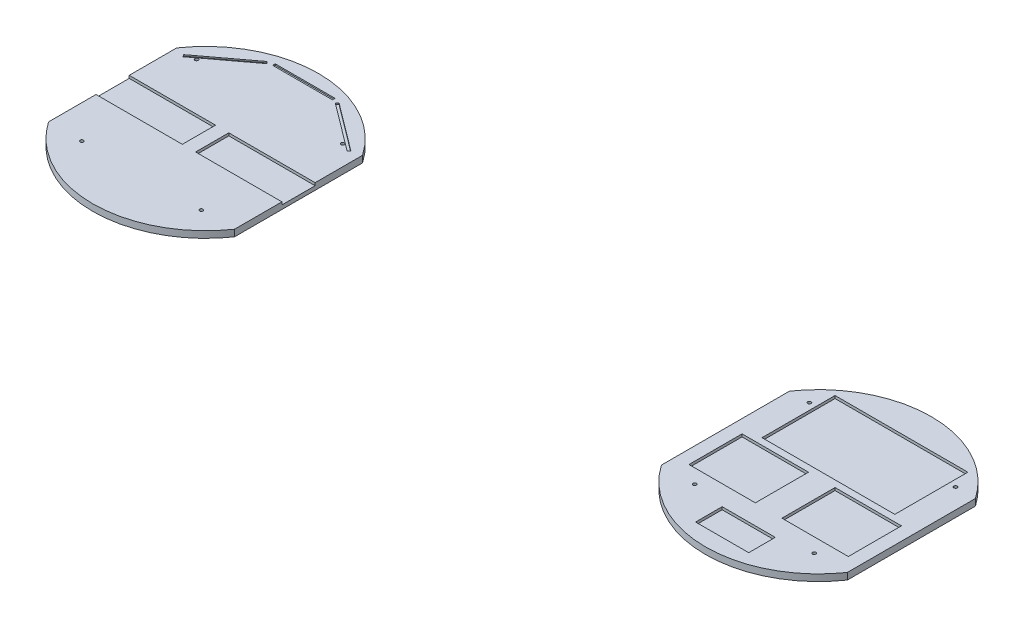
SolidWorks part; units mm, degrees
ref_plane "Front Plane" through (0, 0, 0) normal (0, 0, 1) x (1, 0, 0)
ref_plane "Top Plane" through (0, 0, 0) normal (0, 1, 0) x (1, 0, 0)
ref_plane "Right Plane" through (0, 0, 0) normal (1, 0, 0) x (0, 0, -1)
sketch "Sketch2" plane through (0, 0, 0) normal (0, 1, 0) x (1, 0, 0)
  line L0 (70, -48.2183) -> (70, 48.2183)
  line L1 (85, 0) -> (70, 0)
  line L2 (363.9575, 64.1342) -> (365.1582, 62.5347)
  line L3 (-85, 0) -> (-70, 0)
  line L4 (-70, -48.2183) -> (-70, 48.2183)
  line L5 (-22.5, 75) -> (22.5, 75)
  line L6 (0, 85) -> (0, 75)
  line L7 (70, 12.5) -> (5, 12.5)
  line L8 (-70, -12.5) -> (-5, -12.5)
  line L9 (-70, -12.5) -> (-70, 12.5)
  line L10 (-70, 12.5) -> (-5, 12.5)
  line L11 (-5, -12.5) -> (-5, 12.5)
  line L12 (-63.0208, 46.4718) -> (-27.0329, 73.4879)
  line L13 (478.9844, -44.0639) -> (478.9844, 52.3726)
  line L14 (5, -12.5) -> (5, 12.5)
  line L15 (70, -12.5) -> (5, -12.5)
  line L16 (70, -12.5) -> (70, 12.5)
  line L17 (-45.0269, 59.9798) -> (-51.0305, 67.9771)
  line L18 (45.0269, 59.9798) -> (51.0305, 67.9771)
  line L19 (63.0208, 46.4718) -> (27.0329, 73.4879)
  line L20 (933.5091, -37.1187) -> (933.5091, 59.3178)
  line L21 (347.1643, 49.0267) -> (383.1522, 76.0428)
  line L22 (408.9844, 79.1544) -> (408.9844, 77.1544)
  line L23 (338.9844, -44.0639) -> (338.9844, 52.3726)
  line L24 (386.4844, 79.1544) -> (431.4844, 79.1544)
  line L25 (408.9844, 89.1544) -> (408.9844, 79.1544)
  line L26 (478.9844, 16.6544) -> (413.9844, 16.6544)
  line L27 (338.9844, -8.3456) -> (403.9844, -8.3456)
  line L28 (338.9844, -8.3456) -> (338.9844, 16.6544)
  line L29 (338.9844, 16.6544) -> (403.9844, 16.6544)
  line L30 (403.9844, -8.3456) -> (403.9844, 16.6544)
  line L31 (345.9635, 50.6261) -> (381.9514, 77.6423)
  line L32 (413.9844, -8.3456) -> (413.9844, 16.6544)
  line L33 (478.9844, -8.3456) -> (413.9844, -8.3456)
  line L34 (478.9844, -8.3456) -> (478.9844, 16.6544)
  line L35 (363.9575, 64.1342) -> (357.9539, 72.1315)
  line L36 (454.0113, 64.1342) -> (460.0148, 72.1315)
  line L37 (471.6266, 50.9104) -> (436.0173, 77.6423)
  line L38 (793.5091, -37.1187) -> (793.5091, 59.3178)
  line L39 (386.4844, 77.1544) -> (431.4844, 77.1544)
  line L43 (813.5091, 18.5996) -> (913.5091, 18.5996)
  line L44 (813.5091, 18.5996) -> (813.5091, 73.5996)
  line L45 (813.5091, 73.5996) -> (913.5091, 73.5996)
  line L46 (913.5091, 18.5996) -> (913.5091, 73.5996)
  line L47 (813.5091, 18.5996) -> (913.5091, 73.5996) construction
  line L48 (813.5091, 73.5996) -> (913.5091, 18.5996) construction
  line L52 (454.0113, 64.1342) -> (452.8105, 62.5347)
  line L54 (873.5091, 13.5996) -> (923.5091, 13.5996)
  line L55 (923.5091, -26.4004) -> (923.5091, 13.5996)
  line L60 (873.5091, -26.4004) -> (923.5091, -26.4004)
  line L61 (853.5091, -26.4004) -> (803.5091, -26.4004)
  line L62 (853.5091, -26.4004) -> (853.5091, 13.5996)
  line L63 (853.5091, 13.5996) -> (803.5091, 13.5996)
  line L64 (803.5091, -26.4004) -> (803.5091, 13.5996)
  line L65 (853.5091, -26.4004) -> (803.5091, 13.5996) construction
  line L66 (853.5091, 13.5996) -> (803.5091, -26.4004) construction
  line L67 (873.5091, -26.4004) -> (873.5091, 13.5996)
  line L71 (470.4259, 49.3109) -> (434.8166, 76.0428)
  line L72 (436.0173, 77.6423) -> (434.8166, 76.0428)
  line L73 (843.5091, -61.4004) -> (883.5091, -61.4004)
  line L74 (843.5091, -61.4004) -> (843.5091, -41.4004)
  line L75 (843.5091, -41.4004) -> (883.5091, -41.4004)
  line L76 (883.5091, -61.4004) -> (883.5091, -41.4004)
  line L77 (843.5091, -61.4004) -> (883.5091, -41.4004) construction
  line L78 (843.5091, -41.4004) -> (883.5091, -61.4004) construction
  line L79 (470.4259, 49.3109) -> (471.6266, 50.9104)
  line L80 (381.9514, 77.6423) -> (383.1522, 76.0428)
  line L81 (347.1643, 49.0267) -> (345.9635, 50.6261)
  line L82 (386.4844, 79.1544) -> (386.4844, 77.1544)
  line L83 (431.4844, 79.1544) -> (431.4844, 77.1544)
  circle A0 centre (0, 0) radius 85
  arc A1 (338.9844, -44.0639) -> (478.9844, -44.0639) centre (408.9844, 4.1544) ccw
  arc A2 (478.9844, 52.3726) -> (338.9844, 52.3726) centre (408.9844, 4.1544) ccw
  arc A3 (793.5091, -37.1187) -> (933.5091, -37.1187) centre (863.5091, 11.0996) ccw
  arc A4 (933.5091, 59.3178) -> (793.5091, 59.3178) centre (863.5091, 11.0996) ccw
  circle A9 centre (363.9844, -44.0639) radius 1.25
  circle A10 centre (453.9844, -44.0639) radius 1.25
  circle A11 centre (818.5091, -37.1187) radius 1.25
  circle A12 centre (908.5091, -37.1187) radius 1.25
  circle A13 centre (808.5091, 59.3178) radius 1.25
  circle A14 centre (918.5091, 59.3178) radius 1.25
  circle A15 centre (353.9844, 52.3726) radius 1.25
  circle A16 centre (463.9844, 52.3726) radius 1.25
  dimension "D1" = 15
  dimension "D2" = 170
  dimension "D8" = 170
  dimension "D7" = 170
  dimension "D19" = 15
  dimension "D3" = 10
  dimension "D4" = 45
  dimension "D5" = 65
  dimension "D6" = 25
  dimension "D9" = 10
  dimension "D10" = 45
  dimension "D11" = 65
  dimension "D12" = 25
  dimension "D13" = 100
  dimension "D14" = 55
  dimension "D15" = 40
  dimension "D16" = 50
  dimension "D17" = 20
  dimension "D18" = 40
extrude "Boss-Extrude4" add sketch "Sketch2" along normal blind 4 contours L31 L80 L21 L81 | L24 L83 L39 L82 | L71 L72 L37 L79
extrude "Boss-Extrude5" add sketch "Sketch2<8>" along normal blind 3 separate body contours L27 L30 L29 L23 | L33 L13 L26 L32 region at (371.4844, 0, -4.1544) region at (446.4844, 0, -4.1544)
sketch "Sketch2<8>" plane through (0, 0, 0) normal (0, 1, 0) x (1, 0, 0) same geometry as "Sketch2"
extrude "Boss-Extrude6" add sketch "Sketch2<9>" along normal blind 5 contours L13 A2 L37 L79 L71 L72 L24 L83 L39 L82 L31 L80 L21 L81 L23 L29 L30 L27 A1 L33 L32 L26 A10 A9 A15 A16 region at (408.9878, 0, -3.15)
sketch "Sketch2<9>" plane through (0, 0, 0) normal (0, 1, 0) x (1, 0, 0) same geometry as "Sketch2"
extrude "Boss-Extrude10" add sketch "Sketch2<14>" along normal blind 3 separate body contours L43 L46 L45 L44 | L67 L60 L55 L54 | L73 L76 L75 L74 | L64 L61 L62 L63 region at (863.5091, 0, -46.0996) region at (898.5091, 0, 6.4004) region at (828.5091, 0, 6.4004) region at (863.5091, 0, 51.4004)
sketch "Sketch2<14>" plane through (0, 0, 0) normal (0, 1, 0) x (1, 0, 0) same geometry as "Sketch2"
extrude "Boss-Extrude11" add sketch "Sketch2<15>" along normal blind 5 contours L20 A4 L38 A3 A12 A11 L60 L67 L54 L55 L61 L64 L63 L62 L46 L43 L44 L45 L76 L73 L74 L75 A13 A14 region at (863.5091, 0, -4.137)
sketch "Sketch2<15>" plane through (0, 0, 0) normal (0, 1, 0) x (1, 0, 0) same geometry as "Sketch2"
